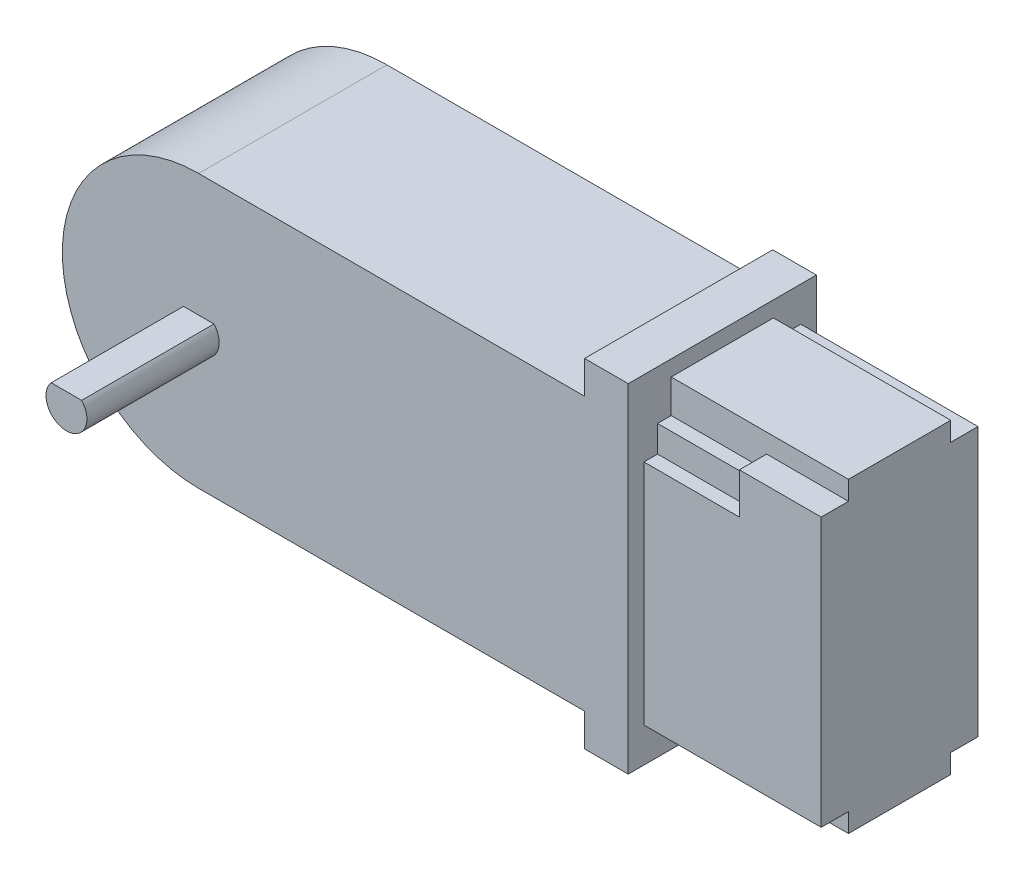
SolidWorks part; units mm, degrees
material "PE Low/Medium Density"
ref_plane "Front Plane" through (0, 0, 0) normal (0, 0, 1) x (1, 0, 0)
ref_plane "Top Plane" through (0, 0, 0) normal (0, 1, 0) x (1, 0, 0)
ref_plane "Right Plane" through (0, 0, 0) normal (1, 0, 0) x (0, 0, -1)
sketch "Sketch1" plane through (0, 0, 0) normal (0, 0, 1) x (1, 0, 0)
  line L0 (-21.1261, 0) -> (52.9977, 0) construction
  line L1 (0, 10) -> (31.5, 10)
  line L2 (0, 10) -> (0, -10)
  line L3 (0, -10) -> (31.5, -10)
  line L4 (31.5, 10) -> (31.5, -10)
  line L5 (31.5, 11.25) -> (44.5, 11.25)
  line L6 (44.5, 11.25) -> (44.5, -11.25)
  line L7 (44.5, -11.25) -> (31.5, -11.25)
  line L9 (31.5, 12.4) -> (28.2955, 12.4)
  line L10 (31.5, 12.4) -> (31.5, -12.4)
  line L11 (31.5, -12.4) -> (28.2955, -12.4)
  line L12 (28.2955, 12.4) -> (28.2955, -12.4)
  circle A0 centre (0, 0) radius 10
  point P11 (-10, 0)
  dimension "D1" = 20
  dimension "D2" = 31.5
  dimension "D3" = 54.5
  dimension "D4" = 22.5
  dimension "D5" = 24.8
extrude "Boss-Extrude1" add sketch "Sketch1" along normal mid plane 13.8 contours L0 A0 L2 | A0 L0 L2 | L2 L0 A0 | L0 L2 A0 | L0 A0 L3 L12 | A0 L0 L12 L1 | L9 L12 L11 L10 region at (-4.2441, 4.2441, 0) region at (-4.2441, -4.2441, 0) region at (4.2441, 4.2441, 0) region at (4.2441, -4.2441, 0) region at (17.9529, 5.2904, 0) region at (17.9529, -5.2904, 0)
extrude "Boss-Extrude2" add sketch "Sketch1<3>" along normal mid plane 11.5 separate body contours L4 L0 L6 L5 L10 | L0 L10 L7 L6 region at (38, 5.625, 0) region at (38, -5.625, 0)
sketch "Sketch1<3>" plane through (0, 0, 0) normal (0, 0, 1) x (1, 0, 0) same geometry as "Sketch1"
sketch "Sketch2" plane through (0, 0, 6.9) normal (0, 0, 1) x (1, 0, 0)
  line L0 (-2.4921, 1) -> (3.6477, 1)
  circle A0 centre (0, 0) radius 1.5
  dimension "D1" = 1
extrude "Boss-Extrude3" add sketch "Sketch2" along normal blind 9.7 contours L0 A0 region at (0, -0.148, 6.9)
sketch "Sketch3" plane through (0, -11.25, 0) normal (0, -1, 0) x (1, 0, 0)
  line L0 (44.5, 5.75) -> (44.5, -5.75) construction
  line L1 (31.5, 5.75) -> (44.5, 5.75)
  line L2 (31.5, 5.75) -> (31.5, 3.75)
  line L3 (31.5, 3.75) -> (44.5, 3.75)
  line L4 (44.5, 5.75) -> (44.5, 3.75)
  line L5 (31.5, 6.9) -> (31.5, -6.9) construction
  line L6 (31.5, -5.75) -> (44.5, -5.75)
  line L7 (31.5, -5.75) -> (31.5, -3.75)
  line L8 (31.5, -3.75) -> (44.5, -3.75)
  line L9 (44.5, -5.75) -> (44.5, -3.75)
  line L10 (44.5, -5.75) -> (31.5, -5.75) construction
  line M1 (31.5, -5.75) -> (44.5, -5.75)
  line M2 (44.5, -5.75) -> (44.5, 5.75)
  line M3 (44.5, 5.75) -> (31.5, 5.75)
  line M4 (31.5, 5.75) -> (31.5, -5.75)
  dimension "D1" = 7.5
  dimension "D2" = 2
extrude "Cut-Extrude1" cut sketch "Sketch3" against normal blind 1.397 contours L3 M4 M2 M3 | L8 M4 M1 M2 region at (38, -11.25, 4.75) region at (38, -11.25, -4.75)
mirror "Mirror1" about plane through (0, 0, 0) normal (0, 1, 0) of "Cut-Extrude1"
sketch "Sketch4" plane through (0, 0, -5.75) normal (0, 0, -1) x (-1, 0, 0)
  line L0 (-38.5, -8.837) -> (-31.5, -8.837)
  line L1 (-31.5, -9.853) -> (-38.5, -9.853)
  line L2 (-31.5, -9.853) -> (-31.5, -6.805)
  line L3 (-31.5, -6.805) -> (-38.5, -6.805)
  line L4 (-38.5, -9.853) -> (-38.5, -6.805)
  line L5 (-31.5, -11.25) -> (-44.5, -11.25) construction
  line M3 (-44.5, -9.853) -> (-31.5, -9.853)
  line M4 (-31.5, -9.853) -> (-31.5, 9.853)
  dimension "D1" = 7
  dimension "D2" = 2.413
  dimension "D3" = 4.445
extrude "Cut-Extrude2" cut sketch "Sketch4" against normal up to surface (2 mm away) contours L4 L0 M3 M4 region at (35, -9.345, -5.75) up to face at (38, -10.5515, -3.75)
extrude "Cut-Extrude3" cut sketch "Sketch4<3>" against normal blind 0.95 contours L4 L0 L3 M4 region at (35, -7.821, -5.75)
sketch "Sketch4<3>" plane through (0, 0, -5.75) normal (0, 0, -1) x (-1, 0, 0) same geometry as "Sketch4"
sketch "Sketch6" plane through (0, 0, 5.75) normal (0, 0, 1) x (1, 0, 0)
  line L0 (38.5, 8.8) -> (31.5, 8.8)
  line L1 (31.5, 9.853) -> (38.5, 9.853)
  line L2 (31.5, 9.853) -> (31.5, 6.853)
  line L3 (31.5, 6.853) -> (38.5, 6.853)
  line L4 (38.5, 9.853) -> (38.5, 6.853)
  line L5 (31.5, 9.853) -> (44.5, 9.853) construction
  line L6 (31.5, 11.25) -> (44.5, 11.25) construction
  line M2 (44.5, 9.853) -> (31.5, 9.853)
  line M3 (31.5, 9.853) -> (31.5, -9.853)
  dimension "D1" = 3
  dimension "D2" = 7
  dimension "D3" = 2.45
extrude "Cut-Extrude4" cut sketch "Sketch6" against normal blind 1 contours L4 L0 L3 M3 region at (35, 7.8265, 5.75)
extrude "Cut-Extrude5" cut sketch "Sketch6<3>" against normal up to surface (2 mm away) contours L4 L0 M2 M3 region at (35, 9.3265, 5.75) up to face at (38, 10.5515, 3.75)
sketch "Sketch6<3>" plane through (0, 0, 5.75) normal (0, 0, 1) x (1, 0, 0) same geometry as "Sketch6"
sketch "Sketch8" plane through (0, 0, 0) normal (0, 0, 1) x (1, 0, 0)
  line L0 (28.2955, 11.9) -> (26.7955, 10.4)
  line L1 (28.2955, 12.4) -> (28.2955, 10) construction
  line L2 (26.7955, 10.4) -> (28.2955, 10.4)
  line L3 (28.2955, 10.4) -> (28.2955, 11.9)
  line L4 (28.2955, 11.9) -> (28.2984, 11.8779)
  line L5 (31.5, 12.4) -> (28.2955, 12.4) construction
  line L6 (28.2955, -10.4) -> (28.2955, -11.9)
  line L7 (28.2955, -10) -> (28.2955, -12.4) construction
  line L8 (28.2955, -11.9) -> (26.7955, -10.4)
  line L9 (26.7955, -10.4) -> (28.2955, -10.4)
  line L10 (31.5, -12.4) -> (28.2955, -12.4) construction
  dimension "D1" = 2
  dimension "D2" = 0.5
  dimension "D3" = 1.5
  dimension "D4" = 0.5
  dimension "D5" = 2
  dimension "D6" = 1.5
extrude "Boss-Extrude4" add sketch "Sketch8" along normal up to surface (3.75 mm away) and the other way up to surface (3.75 mm away) contours L2 L3 L0 | L9 L8 L6 region at (27.7955, 10.9, 0) region at (27.7955, -10.9, 0) up to face at (38.1667, 9.9677, 3.75) other way up to face at (38, 10.5515, -3.75)
